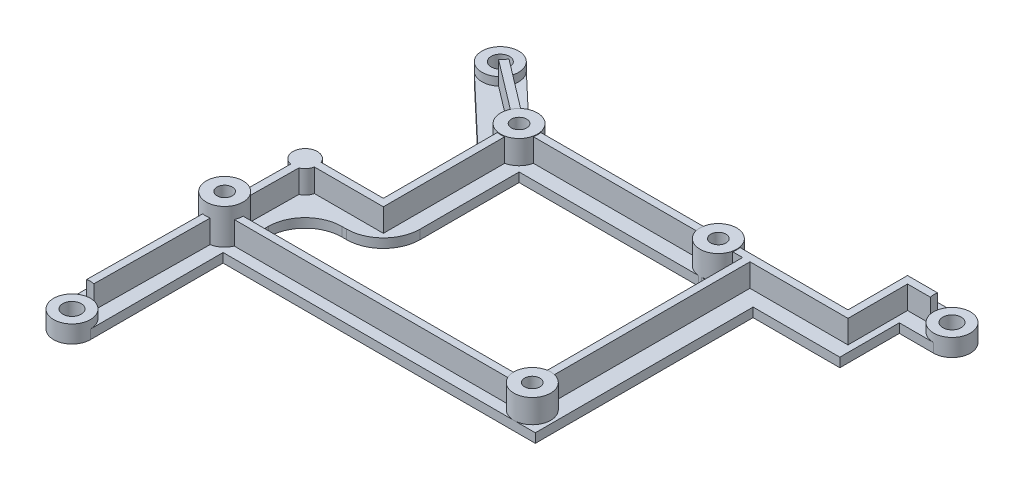
SolidWorks part; units mm, degrees
ref_plane "Płaszczyzna przednia" through (0, 0, 0) normal (0, 0, 1) x (1, 0, 0)
ref_plane "Płaszczyzna górna" through (0, 0, 0) normal (0, 1, 0) x (1, 0, 0)
ref_plane "Płaszczyzna prawa" through (0, 0, 0) normal (1, 0, 0) x (0, 0, -1)
sketch "Szkic1" plane through (0, 0, 0) normal (0, 1, 0) x (1, 0, 0)
  circle A0 centre (0, 0) radius 1.5
  circle A1 centre (0, 0) radius 3
  circle A2 centre (0, 69.85) radius 1.5
  circle A3 centre (0, 69.85) radius 3
  circle A4 centre (73.66, 69.85) radius 1.5
  circle A5 centre (73.66, 69.85) radius 3
  circle A6 centre (73.66, 0) radius 1.5
  circle A7 centre (73.66, 0) radius 3
  dimension "D1" = 3
  dimension "D2" = 6
  dimension "D3" = 3
  dimension "D4" = 6
  dimension "D5" = 3
  dimension "D6" = 6
  dimension "D7" = 3
  dimension "D8" = 6
extrude "Dodanie-wyciągnięcie1" add sketch "Szkic1" against normal blind 7.85
sketch "Szkic2" plane through (0, -7.85, 0) normal (0, -1, 0) x (1, 0, 0)
  line L0 (0, 0) -> (3, 0) construction
  line L1 (75.7037, -67.6538) -> (71.41, -72.1) construction
  line L2 (0, 0) -> (0, 3) construction
  line L3 (0, 0) -> (5.565, 5.565) construction
  line L4 (0, 0) -> (-2.1213, -2.1213) construction
  line L5 (2.1213, 2.1213) -> (75.7037, -67.6538) construction
  line L6 (71.5364, -71.9691) -> (-2.1213, -2.1213) construction
  line L7 (73.66, 0) -> (73.66, -3) construction
  line L8 (73.66, 0) -> (76.66, 0) construction
  line L9 (0, -69.85) -> (-7.397, -62.453) construction
  line L10 (0, -69.85) -> (2.1213, -71.9713) construction
  line L11 (73.66, 0) -> (75.91, -2.25) construction
  line L12 (73.66, 0) -> (70.7837, 2.8763) construction
  line L13 (2.1213, -71.9713) -> (11.4233, -63.1499)
  line L15 (3, 0) -> (3, -5.59)
  line L16 (62.07, -5.59) -> (3, -5.59)
  line L17 (-3, 0) -> (-3, -35.0123)
  line L18 (68.07, -11.59) -> (68.07, -66.85)
  line L19 (73.66, -66.85) -> (68.07, -66.85)
  line L20 (73.66, -72.85) -> (64.7409, -72.85)
  line L21 (64.7409, -72.85) -> (64.7409, -63.1499)
  line L22 (11.4233, -63.1499) -> (64.7409, -63.1499)
  line L25 (9.7645, -41.0123) -> (3, -41.0123)
  line L26 (9.7645, -35.0123) -> (9, -35.0123)
  line L27 (9.7645, -53.878) -> (9.7645, -41.0123)
  line L28 (15.7645, -41.0123) -> (15.7645, -57.1499)
  line L29 (36.83, -39.0579) -> (75.7813, -2.1213) construction
  line L30 (15.7645, -57.1499) -> (56.07, -57.1499)
  line L31 (62.07, -51.1499) -> (62.07, -27.64)
  line L32 (9, -11.59) -> (56.07, -11.59)
  line L33 (3, -17.59) -> (3, -21.64)
  line L34 (62.07, -21.64) -> (3, -21.64)
  line L35 (62.07, -27.64) -> (3, -27.64)
  line L36 (3, -27.64) -> (3, -29.0123)
  line L37 (62.07, -21.64) -> (62.07, -17.59)
  line L41 (-2.1213, -67.7287) -> (7.8932, -58.2316)
  arc A0 (3, 0) -> (-3, 0) centre (0, 0) ccw
  arc A4 (73.66, -72.85) -> (73.66, -66.85) centre (73.66, -69.85) ccw
  circle A10 centre (0, 0) radius 1.5
  circle A11 centre (0, -69.85) radius 1.5
  circle A12 centre (73.66, -69.85) radius 1.5
  arc A13 (15.7645, -41.0123) -> (9.7645, -35.0123) centre (9.7645, -41.0123) ccw
  arc A17 (9.7645, -53.878) -> (7.8932, -58.2316) centre (3.7645, -53.878) cw
  arc A19 (62.07, -51.1499) -> (56.07, -57.1499) centre (56.07, -51.1499) cw
  arc A21 (9, -11.59) -> (3, -17.59) centre (9, -17.59) ccw
  arc A22 (62.07, -17.59) -> (56.07, -11.59) centre (56.07, -17.59) ccw
  arc A23 (3, -29.0123) -> (9, -35.0123) centre (9, -29.0123) ccw
  arc A24 (-3, -35.0123) -> (3, -41.0123) centre (3, -35.0123) ccw
  arc A25 (68.07, -11.59) -> (62.07, -5.59) centre (62.07, -11.59) ccw
  circle A26 centre (11.555, -24.64) radius 3 construction
  arc A34 (-2.1213, -67.7287) -> (2.1213, -71.9713) centre (0, -69.85) ccw
  point P45 (11.4239, -63.1499)
  dimension "D5" = 6
  dimension "D6" = 6
  dimension "D7" = 6
  dimension "D8" = 6
  dimension "D9" = 6
  dimension "D10" = 6
extrude "Dodanie-wyciągnięcie2" add sketch "Szkic2" against normal blind 1.5
sketch "Szkic4" plane through (0, -6.35, 0) normal (0, 1, 0) x (1, 0, 0)
  line L1 (66.3126, 7.3474) -> (60.3126, 13.3474) construction
  circle A3 centre (64.9195, 8.7824) radius 2
  circle A5 centre (0.1716, 37.8407) radius 2
extrude "Dodanie-wyciągnięcie4" add sketch "Szkic4" along normal up to surface (3.75 mm away)
sketch "Szkic5" plane through (0, -7.85, 0) normal (0, -1, 0) x (1, 0, 0)
  circle A1 centre (73.66, 0) radius 3
extrude "Wytnij-wyciągnięcie1" cut sketch "Szkic5" against normal through all
sketch "Szkic7" plane through (0, -7.85, 0) normal (0, -1, 0) x (1, 0, 0)
  line L1 (3, -21.64) -> (69.939, -21.64)
  line L2 (3, -21.64) -> (3, 0)
  line L3 (3, 0) -> (69.939, 0)
  line L4 (69.939, -21.64) -> (69.939, 0)
extrude "Wytnij-wyciągnięcie3" cut sketch "Szkic7" against normal through all
sketch "Szkic6" plane through (0, -7.85, 0) normal (0, -1, 0) x (1, 0, 0)
  line L0 (0.254, -24.6414) -> (0.254, -29.8643) construction
  line L1 (0.254, -24.6414) -> (59.2799, -24.6414) construction
  line L2 (50.419, -24.6414) -> (50.419, -29.0866) construction
  circle A0 centre (0.254, -24.6414) radius 1.25
  circle A1 centre (50.419, -24.6414) radius 1.25
  circle A2 centre (0.254, -24.6414) radius 3
  circle A3 centre (50.419, -24.6414) radius 3
  circle A4 centre (0.254, -24.6414) radius 0.6 construction
  dimension "D1" = 2.5
  dimension "D2" = 2.5
  dimension "D3" = 6
  dimension "D4" = 6
  dimension "D5" = 1.2
sketch "Szkic8" plane through (0, -7.85, 0) normal (0, -1, 0) x (1, 0, 0)
  line L1 (46.919, -21.64) -> (53.919, -21.64)
  line L2 (46.919, -21.64) -> (46.919, -63.1499)
  line L3 (46.919, -63.1499) -> (53.919, -63.1499)
  line L4 (53.919, -21.64) -> (53.919, -63.1499)
  circle A0 centre (50.419, -24.6414) radius 1.25 construction
  dimension "D1" = 3.5
  dimension "D2" = 3.5
extrude "Dodanie-wyciągnięcie5" add sketch "Szkic8" against normal up to surface (1.5 mm away)
sketch "Szkic9" plane through (0, -7.85, 0) normal (0, -1, 0) x (1, 0, 0)
  line L1 (53.919, -57.1499) -> (82.778, -57.1499)
  line L2 (53.919, -57.1499) -> (53.919, -12.1918)
  line L3 (53.919, -12.1918) -> (82.778, -12.1918)
  line L4 (82.778, -57.1499) -> (82.778, -12.1918)
extrude "Wytnij-wyciągnięcie4" cut sketch "Szkic9" against normal through all
extrude "Dodanie-wyciągnięcie6" add sketch "Szkic6" against normal blind 7.25
sketch "Szkic10" plane through (0, -0.6, 0) normal (0, 1, 0) x (1, 0, 0)
  circle A0 centre (50.419, 24.6414) radius 1.25
  circle A1 centre (0.254, 24.6414) radius 1.25
extrude "Wytnij-wyciągnięcie5" cut sketch "Szkic10" against normal up to surface (7.25 mm away)
sketch "Szkic12" plane through (0, -0.6, 0) normal (0, 1, 0) x (1, 0, 0)
  circle A0 centre (50.419, 24.6414) radius 3
extrude "Wytnij-wyciągnięcie6" cut sketch "Szkic12" against normal blind 1.9
sketch "Szkic11" plane through (0, -7.85, 0) normal (0, -1, 0) x (1, 0, 0)
  line L0 (15.7645, -57.1499) -> (15.7645, -63.1499) construction
  line L1 (15.7645, -63.1499) -> (7.3726, -63.1499) construction
  line L2 (9.7645, -53.878) -> (9.7645, -68.6584) construction
  line L3 (15.7645, -57.5302) -> (4.2778, -57.5302) construction
  line L4 (15.7645, -63.1499) -> (9.7645, -57.5302) construction
  line L5 (15.7645, -57.5302) -> (9.7645, -63.1499) construction
  line L6 (12.7645, -60.3401) -> (12.7645, -58.4162) construction
  line L7 (42.2645, -66.5432) -> (42.2645, -50.5482) construction
  line L8 (12.7645, -60.1401) -> (46.7614, -60.1401) construction
  circle A1 centre (12.7645, -60.3401) radius 0.2 construction
  circle A2 centre (12.7645, -60.1401) radius 3
  circle A3 centre (42.2645, -60.1401) radius 3 construction
  circle A4 centre (45.2645, -60.1401) radius 3
  dimension "D1" = 26.5
  dimension "D3" = 6
  dimension "D2" = 5.6198
extrude "Dodanie-wyciągnięcie7" add sketch "Szkic11" against normal up to surface (5.35 mm away)
sketch "Szkic13" plane through (0, -2.5, 0) normal (0, 1, 0) x (1, 0, 0)
  circle A0 centre (45.2645, 60.1401) radius 1.25
  circle A1 centre (12.7645, 60.1401) radius 1.25
  dimension "D1" = 2.5
  dimension "D2" = 2.5
extrude "Wytnij-wyciągnięcie8" cut sketch "Szkic13" against normal through all
sketch "Szkic14" plane through (0, 0, 0) normal (0, 1, 0) x (1, 0, 0)
  circle A0 centre (0, 0) radius 3
  circle A1 centre (0, 69.85) radius 3
  circle A2 centre (73.66, 69.85) radius 3
extrude "Wytnij-wyciągnięcie9" cut sketch "Szkic14" against normal blind 5
sketch "Szkic15" plane through (0, -6.35, 0) normal (0, 1, 0) x (1, 0, 0)
  line L0 (0, 0) -> (0.0208, 1.9717) construction
  line L5 (0.254, 24.0552) -> (50.419, 24.0552) construction
  line L6 (50.419, 24.0552) -> (50.419, 71.5126) construction
  line L7 (45.2645, 60.1401) -> (12.7645, 60.1401) construction
  line L8 (12.7645, 60.1401) -> (2.3877, 68.0337) construction
  line L9 (45.2645, 60.1401) -> (73.8303, 60.1401) construction
  line L11 (68.07, 64.9563) -> (64.7409, 64.9563) construction
  line L12 (66.4054, 69.85) -> (66.4054, 60.1401) construction
  line L13 (12.7645, 60.1401) -> (12.7645, 33.3303) construction
  line L14 (9, 35.0123) -> (21.3665, 35.0123) construction
  line L15 (9.7645, 41.0123) -> (9.7645, 35.0123) construction
  line L16 (12.7645, 38.0123) -> (0.4014, 38.0123) construction
  line L19 (0.6311, 2.9329) -> (0.8312, 21.6944)
  line L20 (0.8312, 21.6944) -> (-0.3731, 21.6944)
  line L24 (0.8784, 26.1232) -> (-0.3268, 26.1232)
  line L27 (-0.3268, 26.1232) -> (-0.1962, 38.6123)
  line L28 (0.8784, 26.1232) -> (0.9989, 37.4123)
  line L29 (12.1645, 57.7528) -> (12.1645, 38.6123)
  line L30 (-0.1962, 38.6123) -> (12.1645, 38.6123)
  line L31 (0.9989, 37.4123) -> (13.3645, 37.4123)
  line L32 (13.3645, 57.7528) -> (13.3645, 37.4123)
  line L33 (13.3645, 57.7528) -> (12.1645, 57.7528)
  line L34 (48.2108, 24.6552) -> (48.2108, 23.4552)
  line L35 (48.2108, 23.4552) -> (2.1302, 23.4552)
  line L36 (2.1302, 24.6552) -> (2.1302, 23.4552)
  line L37 (48.2108, 24.6552) -> (2.1302, 24.6552)
  line L38 (51.019, 26.1232) -> (49.819, 26.1232)
  line L39 (49.819, 26.1232) -> (49.819, 59.5401)
  line L40 (51.019, 26.1232) -> (51.019, 59.5401)
  line L41 (67.0054, 59.5401) -> (51.019, 59.5401)
  line L42 (65.8054, 60.7401) -> (47.6678, 60.7401)
  line L43 (65.8054, 60.7401) -> (65.8054, 70.45)
  line L44 (67.0054, 60.1401) -> (67.0054, 69.25)
  line L45 (67.0054, 60.1401) -> (67.0054, 59.5401)
  line L46 (49.819, 59.5401) -> (47.6678, 59.5401)
  line L48 (70.7206, 69.25) -> (67.0054, 69.25)
  line L49 (70.7206, 70.45) -> (65.8054, 70.45)
  line L50 (47.6678, 59.5401) -> (47.6678, 60.7401)
  line L51 (43.2946, 59.5401) -> (43.2946, 60.7401)
  line L52 (43.2946, 59.5401) -> (14.6986, 59.5401)
  line L53 (43.2946, 60.7401) -> (14.6986, 60.7401)
  line L54 (14.6986, 59.5401) -> (14.6986, 60.7401)
  line L56 (11.3866, 61.9421) -> (10.6601, 60.987)
  line L57 (10.6601, 60.987) -> (1.9762, 67.5929)
  line L58 (11.3866, 61.9421) -> (2.7027, 68.5479)
  line L60 (-0.569, 2.9455) -> (-0.3731, 21.6944)
  line L61 (0.0317, 2.9998) -> (0.2291, 21.6944) construction
  line L62 (70.66, 69.85) -> (65.8054, 69.85) construction
  arc A1 (1.9762, 67.5929) -> (2.7027, 68.5479) centre (0, 69.85) ccw
  arc A2 (0.6311, 2.9329) -> (-0.569, 2.9455) centre (0, 0) ccw
  arc A3 (70.7206, 70.45) -> (70.7206, 69.25) centre (73.66, 69.85) ccw
  dimension "D4" = 90
extrude "Dodanie-wyciągnięcie8" add sketch "Szkic15" along normal up to surface (3.75 mm away)
